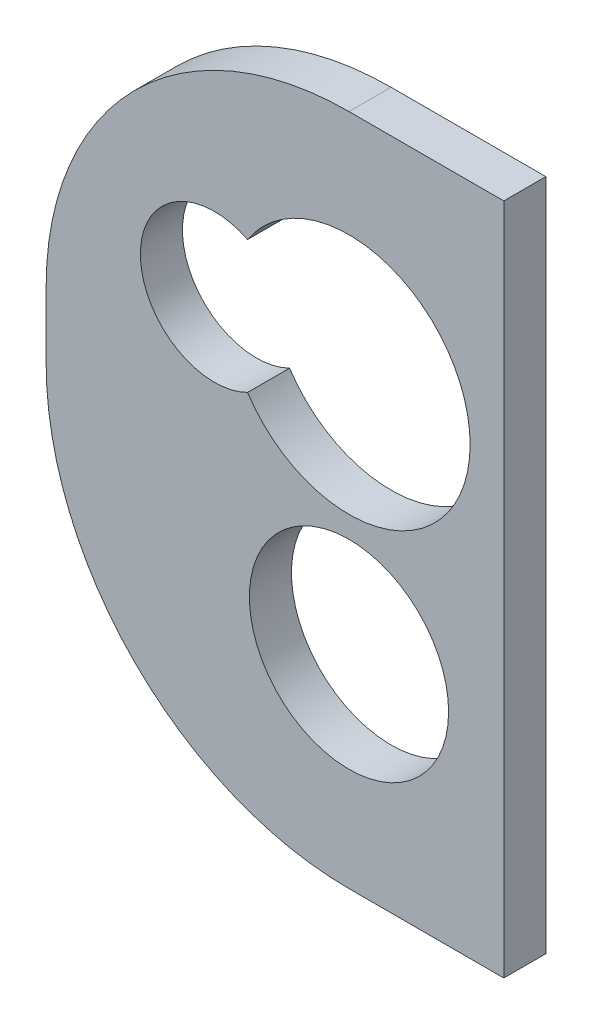
SolidWorks part; units mm, degrees
material "Balsa"
ref_plane "Front Plane" through (0, 0, 0) normal (0, 0, 1) x (1, 0, 0)
ref_plane "Top Plane" through (0, 0, 0) normal (0, 1, 0) x (1, 0, 0)
ref_plane "Right Plane" through (0, 0, 0) normal (1, 0, 0) x (0, 0, -1)
sketch "Sketch1" plane through (0, 0, 0) normal (0, 0, 1) x (1, 0, 0)
  line L0 (0, -1000.1535) -> (0, 48999.8465) construction
  line L2 (-1000, 0) -> (49000, 0) construction
  line L3 (5.842, 17.7413) -> (0, 17.7413)
  line L4 (5.842, 17.7413) -> (5.842, -7.6587)
  line L6 (5.842, -7.6587) -> (0, -7.6587)
  line L7 (-11.43, 6.3113) -> (-11.43, 3.7713)
  circle A0 centre (0, 0) radius 3.7592
  arc A1 (-3.829, 6.6457) -> (-3.829, 11.6423) centre (0, 9.144) ccw
  arc A2 (-3.829, 11.6423) -> (-3.829, 6.6457) centre (-5.08, 9.144) ccw
  arc A3 (0, 17.7413) -> (-11.43, 6.3113) centre (0, 6.3113) ccw
  arc A4 (0, -7.6587) -> (-11.43, 3.7713) centre (0, 3.7713) cw
  dimension "D1" = 7.5184
  dimension "D4" = 25.4
  dimension "D3" = 9.144
  dimension "D5" = 5.588
  dimension "D9" = 11.43
  dimension "D10" = 11.43
  dimension "D2" = 5.842
  dimension "D6" = 9.144
  dimension "D7" = 5.08
  dimension "D8" = 6.35
extrude "Boss-Extrude1" add sketch "Sketch1" along normal blind 1.5875
